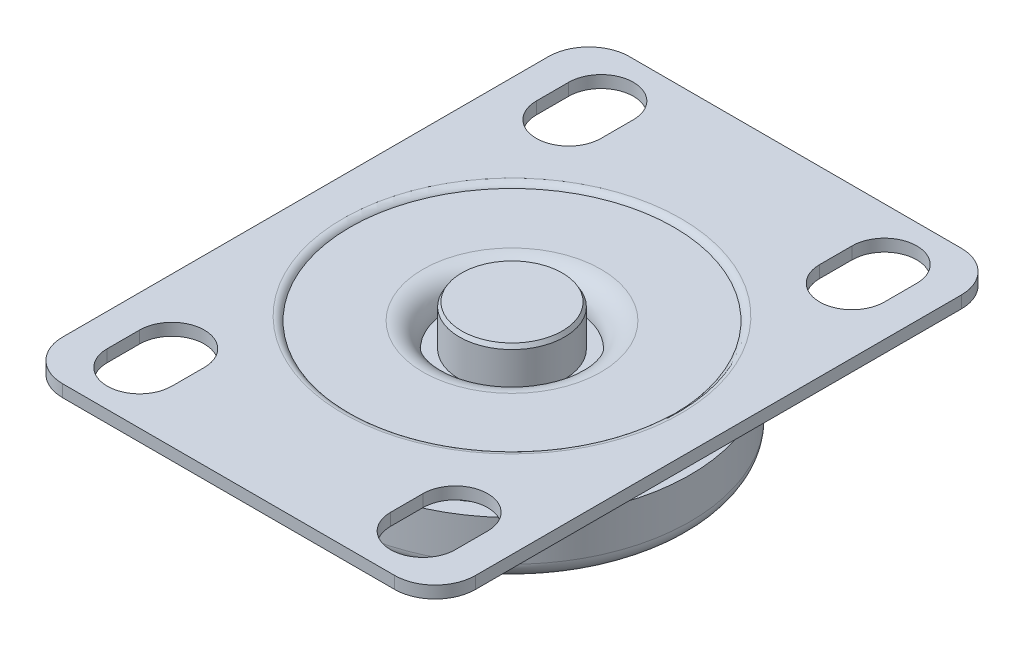
SolidWorks part; units mm, degrees
ref_plane "Front Plane" through (0, 0, 0) normal (0, 0, 1) x (1, 0, 0)
ref_plane "Top Plane" through (0, 0, 0) normal (0, 1, 0) x (1, 0, 0)
ref_plane "Right Plane" through (0, 0, 0) normal (1, 0, 0) x (0, 0, -1)
sketch "Sketch1" plane through (0, 0, 0) normal (0, 1, 0) x (1, 0, 0)
  line L1 (-20.5, -35) -> (20.5, -35)
  line L2 (-25.5, -30) -> (-25.5, 30)
  line L3 (-20.5, 35) -> (20.5, 35)
  line L4 (25.5, -30) -> (25.5, 30)
  line L5 (-25.5, -35) -> (25.5, 35) construction
  line L6 (-25.5, 35) -> (25.5, -35) construction
  arc A0 (-20.5, -35) -> (-25.5, -30) centre (-20.5, -30) cw
  arc A1 (20.5, -35) -> (25.5, -30) centre (20.5, -30) ccw
  arc A2 (20.5, 35) -> (25.5, 30) centre (20.5, 30) cw
  arc A3 (-25.5, 30) -> (-20.5, 35) centre (-20.5, 30) cw
  point P0 (0, 0)
  dimension "D3" = 5
  dimension "D1" = 51
  dimension "D2" = 70
extrude "Boss-Extrude1" add sketch "Sketch1" along normal blind 1.5
sketch "Sketch2" plane through (0, 1.5, 0) normal (0, 1, 0) x (1, 0, 0)
  line L0 (-17.5, 24.5) -> (-17.5, 28.5) construction
  line L1 (-17.5, -26.5) -> (17.5, -26.5) construction
  line L2 (-17.5, -26.5) -> (-17.5, 26.5) construction
  line L3 (-17.5, 26.5) -> (17.5, 26.5) construction
  line L4 (17.5, -26.5) -> (17.5, 26.5) construction
  line L5 (-17.5, -26.5) -> (17.5, 26.5) construction
  line L6 (-17.5, 26.5) -> (17.5, -26.5) construction
  line L7 (-21.5, 24.5) -> (-21.5, 28.5)
  line L8 (-13.5, 24.5) -> (-13.5, 28.5)
  line L9 (17.5, 24.5) -> (17.5, 28.5) construction
  line L10 (13.5, 24.5) -> (13.5, 28.5)
  line L11 (21.5, 24.5) -> (21.5, 28.5)
  arc A0 (-21.5, 24.5) -> (-13.5, 24.5) centre (-17.5, 24.5) ccw
  arc A1 (-13.5, 28.5) -> (-21.5, 28.5) centre (-17.5, 28.5) ccw
  arc A2 (13.5, 24.5) -> (21.5, 24.5) centre (17.5, 24.5) ccw
  arc A3 (21.5, 28.5) -> (13.5, 28.5) centre (17.5, 28.5) ccw
  point P0 (0, 0)
  point P8 (-17.5, 26.5)
  point P14 (17.5, 26.5)
  dimension "D3" = 4
  dimension "D5" = 4
  dimension "D6" = 4
  dimension "D1" = 35
  dimension "D2" = 53
  dimension "D4" = 4
extrude "Cut-Extrude1" cut sketch "Sketch2" against normal blind 2
mirror "Mirror1" about plane through (0, 0, 0) normal (0, 0, 1) of "Cut-Extrude1"
sketch "Sketch3" plane through (0, 1.5, 0) normal (0, 1, 0) x (1, 0, 0)
  circle A0 centre (0, 0) radius 4
  dimension "D1" = 8
extrude "Cut-Extrude2" cut sketch "Sketch3" against normal blind 2
sketch "Sketch4" plane through (0, 1.5, 0) normal (0, 1, 0) x (1, 0, 0)
  circle A0 centre (0, 0) radius 20
  dimension "D1" = 40
extrude "Cut-Extrude3" cut sketch "Sketch4" against normal blind 0.5
fillet "Fillet1" radius 1 1 edges at (0, 1.5, 20)
sketch "Sketch5" plane through (0, 0, 0) normal (0, -1, 0) x (1, 0, 0)
  circle A0 centre (0, 0) radius 22
  dimension "D1" = 44
extrude "Boss-Extrude2" add sketch "Sketch5" along normal blind 3
sketch "Sketch6" plane through (0, 1, 0) normal (0, 1, 0) x (1, 0, 0)
  circle A0 centre (0, 0) radius 6.5
  dimension "D1" = 13
extrude "Boss-Extrude3" add sketch "Sketch6" along normal blind 2
chamfer "Chamfer1" distance 0.5 angle 30 1 edges at (0, 3, 6.5) first distance on face at (0, 3, 6.5)
sketch "Sketch7" plane through (0, -3, 0) normal (0, -1, 0) x (1, 0, 0)
  circle A0 centre (0, 0) radius 7.5
  dimension "D1" = 15
extrude "Boss-Extrude4" add sketch "Sketch7" along normal blind 1.5
sketch "Sketch8" plane through (0, -4.5, 0) normal (0, -1, 0) x (1, 0, 0)
  circle A0 centre (0, 0) radius 22
extrude "Boss-Extrude5" add sketch "Sketch8" along normal blind 7
fillet "Fillet3" radius 2 1 edges at (0, -11.5, -22)
sketch "Sketch9" plane through (0, 1, 0) normal (0, 1, 0) x (1, 0, 0)
  circle A0 centre (0, 0) radius 6.5
  circle A1 centre (0, 0) radius 8
  dimension "D1" = 16
extrude "Cut-Extrude4" cut sketch "Sketch9" against normal blind 3
fillet "Fillet4" radius 3 1 edges at (0, 1, 8)
